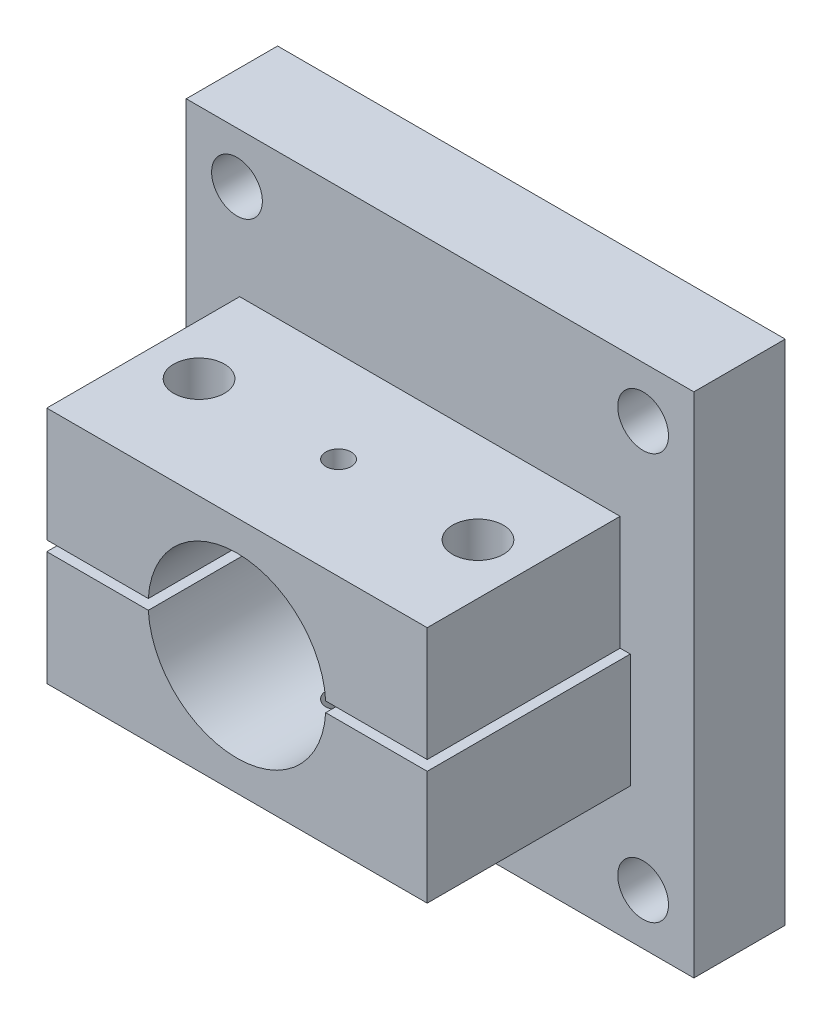
SolidWorks part; units mm, degrees
material "6061-T6 (SS)"
ref_plane "Front Plane" through (0, 0, 0) normal (0, 0, 1) x (1, 0, 0)
ref_plane "Top Plane" through (0, 0, 0) normal (0, 1, 0) x (1, 0, 0)
ref_plane "Right Plane" through (0, 0, 0) normal (1, 0, 0) x (0, 0, -1)
sketch "Sketch1" plane through (0, 0, 0) normal (0, 0, 1) x (1, 0, 0)
  line L0 (0, 31.75) -> (0, -31.75) construction
  line L1 (-31.75, 31.75) -> (31.75, 31.75)
  line L2 (-31.75, 31.75) -> (-31.75, -31.75)
  line L3 (-31.75, -31.75) -> (31.75, -31.75)
  line L4 (31.75, 31.75) -> (31.75, -31.75)
  line L5 (-31.75, 0) -> (31.75, 0) construction
  line L6 (-31.75, 0) -> (-31.75, -0.635)
  line L7 (-31.75, -0.635) -> (0, -0.635) construction
  line L8 (0, -0.635) -> (-11.0943, -0.635) construction
  line L9 (-11.0943, -0.635) -> (-23.7943, -0.635)
  line L10 (-23.7943, -0.635) -> (-23.7943, -14.9225)
  line L11 (-23.7943, -14.9225) -> (23.7943, -14.9225)
  line L12 (11.0943, -0.635) -> (23.7943, -0.635)
  line L13 (23.7943, -0.635) -> (23.7943, -14.9225)
  line L14 (11.0943, 0.635) -> (23.7943, 0.635)
  line L15 (23.7943, 0.635) -> (23.7943, 14.9225)
  line L16 (-23.7943, 14.9225) -> (23.7943, 14.9225)
  line L17 (-23.7943, 0.635) -> (-23.7943, 14.9225)
  line L18 (-11.0943, 0.635) -> (-23.7943, 0.635)
  circle A0 centre (0, 0) radius 11.1125
  circle A1 centre (25.4, 25.4) radius 3.175
  circle A2 centre (-25.4, 25.4) radius 3.175
  circle A3 centre (25.4, -25.4) radius 3.175
  circle A4 centre (-25.4, -25.4) radius 3.175
  point P28 (0, -14.9225)
  dimension "D1" = 22.225
  dimension "D5" = 6.35
  dimension "D3" = 6.35
  dimension "D4" = 6.35
  dimension "D6" = 0.635
  dimension "D7" = 14.9225
  dimension "D8" = 12.7
extrude "Boss-Extrude1" add sketch "Sketch1" along normal blind 6.35 contours L4 L1 L2 L3 A4 A2 A1 A0 L18 L17 L16 L15 L14 L12 L13 L11 L10 L9 A3 | A0 L14 L15 L16 L17 L18 | A0 L9 L10 L11 L13 L12 region at (0, 30.852, 0) region at (0, -11.6094, 0) region at (-17.4443, 1.1319, 0)
extrude "Boss-Extrude2" add sketch "Sketch1<3>" along normal blind 31.75 contours A0 L9 L10 L11 L13 L12 region at (0, -11.6094, 0)
sketch "Sketch1<3>" plane through (0, 0, 0) normal (0, 0, 1) x (1, 0, 0) same geometry as "Sketch1"
extrude "Boss-Extrude3" add sketch "Sketch1<4>" against normal blind 24.13 from surface separate body contours A0 L14 L15 L16 L17 L18 region at (-17.4443, 1.1319, 0) starting at face at (0, -7.1437, 31.75)
sketch "Sketch1<4>" plane through (0, 0, 0) normal (0, 0, 1) x (1, 0, 0) same geometry as "Sketch1"
sketch "Sketch2" plane through (0, 0, 0) normal (0, 1, 0) x (1, 0, 0)
  line L0 (0, 0) -> (0, -6.35) construction
  line L1 (0, -6.35) -> (0, -31.75) construction
  line L2 (0, -19.05) -> (11.0943, -19.05) construction
  line L5 (11.0943, -19.05) -> (23.7943, -19.05) construction
  line L6 (23.7943, -31.75) -> (23.7943, -6.35) construction
  line L7 (11.0943, -31.75) -> (11.0943, -6.35) construction
  circle A0 centre (17.4443, -19.05) radius 3.175
  circle A1 centre (-17.4443, -19.05) radius 3.175
  circle A2 centre (0, -19.05) radius 1.5875
  dimension "D3" = 6.35
  dimension "D1" = 6.35
  dimension "D4" = 3.175
  dimension "D2" = 25.4
extrude "Cut-Extrude1" cut sketch "Sketch2" against normal through all both and the other way through all
extrude "Boss-Extrude4" add sketch "Sketch1<5>" against normal blind 5.08 contours L4 L1 L2 L3 A4 A2 A1 A0 L18 L17 L16 L15 L14 L12 L13 L11 L10 L9 A3 | A0 L14 L15 L16 L17 L18 | A0 | A0 L9 L10 L11 L13 L12 region at (0, 30.852, 0) region at (0, -11.6094, 0) region at (0, 0, 0) region at (-17.4443, 1.1319, 0)
sketch "Sketch1<5>" plane through (0, 0, 0) normal (0, 0, 1) x (1, 0, 0) same geometry as "Sketch1"
equation "\"Shaft Diameter\"= 7 / 8"
equation "\"Overall Width\"= 2.5"
equation "\"Overall Height\"= 1.25"
equation "\"Bolt Diameter Plate\"= 1 / 4"
equation "\"Bolt Diameter Bracket\"= 1 / 4"
equation "\"D3@Sketch1\"=.25"
equation "\"D2@Sketch1\"=\"Overall Width\""
equation "\"D1@Sketch1\"=\"Shaft Diameter\""
equation "\"Bolt From Edge\"= .25"
equation "\"D4@Sketch1\"=\"Bolt Diameter Plate\""
equation "\"D5@Sketch1\"=\"Bolt Diameter Plate\""
equation "\"Bracket Gap\"= .05"
equation "\"Bracket Plate Thickness\" = .25"
equation "\"D6@Sketch1\"=\"Bracket Gap\"/2"
equation "\"D7@Sketch1\"=\"Shaft Diameter\"/2+.15"
equation "\"D8@Sketch1\"=\"Bolt Diameter Bracket\"*2"
equation "\"D1@Boss-Extrude1\"=\"Bracket Plate Thickness\""
equation "\"D1@Boss-Extrude2\"=\"Overall Height\""
equation "\"D1@Sketch2\"=\"Bolt Diameter Plate\""
equation "\"D2@Sketch2\"=\"Overall Height\"-\"Bolt Diameter Plate\""
equation "\"D3@Sketch2\"=\"Bolt Diameter Bracket\""
equation "\"D1@Boss-Extrude3\"=\"Overall Height\"-\"Bracket Plate Thickness\"-.05"
equation "\"Pin bolt diameter\"= 1 / 8"
equation "\"D4@Sketch2\"=\"Pin bolt diameter\""
